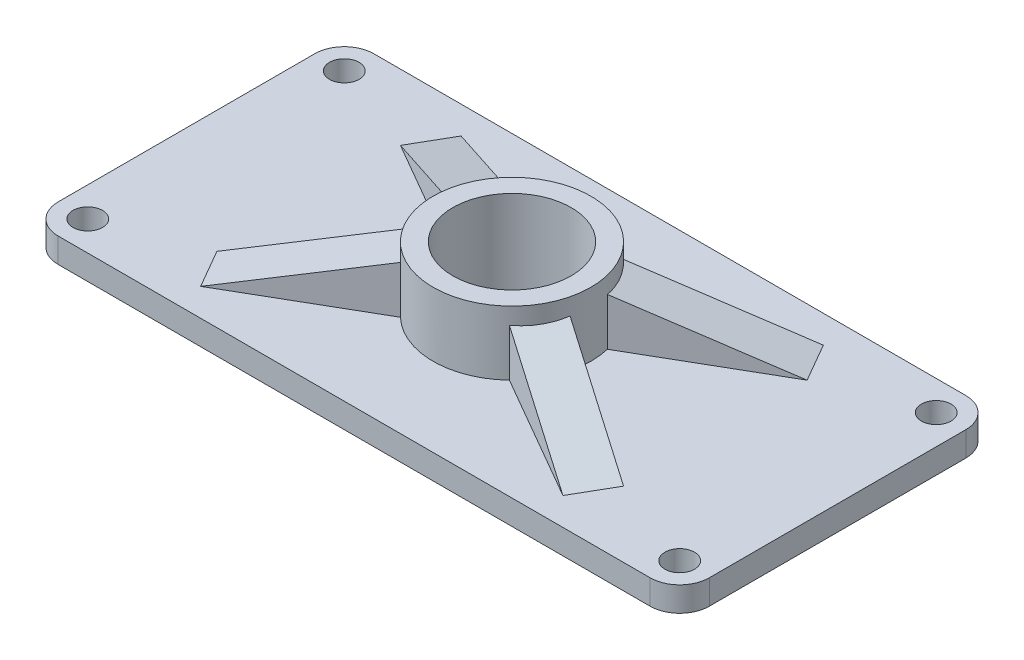
SolidWorks part; units mm, degrees
ref_plane "Front Plane" through (0, 0, 0) normal (0, 0, 1) x (1, 0, 0)
ref_plane "Top Plane" through (0, 0, 0) normal (0, 1, 0) x (1, 0, 0)
ref_plane "Right Plane" through (0, 0, 0) normal (1, 0, 0) x (0, 0, -1)
sketch "Sketch1" plane through (0, 0, 0) normal (0, 1, 0) x (1, 0, 0)
  line L1 (-60, 32) -> (60, 32)
  line L2 (-66, 26) -> (-66, -26)
  line L3 (-60, -32) -> (60, -32)
  line L4 (66, 26) -> (66, -26)
  line L5 (-66, 32) -> (66, -32) construction
  line L6 (-66, -32) -> (66, 32) construction
  arc A0 (60, 32) -> (66, 26) centre (60, 26) cw
  arc A1 (-66, -26) -> (-60, -32) centre (-60, -26) ccw
  arc A2 (-60, 32) -> (-66, 26) centre (-60, 26) ccw
  arc A3 (60, -32) -> (66, -26) centre (60, -26) ccw
  circle A4 centre (-60, 26) radius 3
  circle A5 centre (-60, -26) radius 3
  circle A6 centre (60, 26) radius 3
  circle A7 centre (60, -26) radius 3
  point P0 (0, 0)
  dimension "D3" = 6
  dimension "D4" = 6
  dimension "D5" = 6
  dimension "D6" = 6
  dimension "D7" = 6
  dimension "D1" = 64
  dimension "D2" = 132
extrude "Boss-Extrude1" add sketch "Sketch1" along normal blind 5
sketch "Sketch2" plane through (0, 5, 0) normal (0, 1, 0) x (1, 0, 0)
  circle A0 centre (0, 0) radius 12
  circle A1 centre (0, 0) radius 16
  dimension "D1" = 32
  dimension "D2" = 24
extrude "Cut-Extrude1" cut sketch "Sketch2" against normal blind 5 contours A0
extrude "Boss-Extrude2" add sketch "Sketch2<3>" along normal blind 13
sketch "Sketch2<3>" plane through (0, 5, 0) normal (0, 1, 0) x (1, 0, 0) same geometry as "Sketch2"
sketch "Sketch3" plane through (0, 5, 0) normal (0, 1, 0) x (1, 0, 0)
  line L0 (-75.8789, 0) -> (75.8789, 0) construction
  line L1 (0, -45.5996) -> (0, 45.5996) construction
  line L2 (-79.2846, -45.775) -> (79.2846, 45.775) construction
  line L3 (80.5101, -46.4825) -> (-80.5101, 46.4825) construction
  point P6 (0, 0)
  point P10 (0, 0)
  point P13 (0, 0)
  point P16 (0, 0)
  dimension "D1" = 30
  dimension "D2" = 30
ref_plane "Plane1" through (0, 0, 0) normal (0.5, 0, 0.866) x (0.866, 0, -0.5)
sketch "Sketch4" plane through (0, 0, 0) normal (0.5, 0, 0.866) x (0.866, 0, -0.5)
  line L0 (-45, 5) -> (-14.7048, 14.8435)
  line L1 (-65.7131, 5) -> (65.7131, 5) construction
  line L3 (-14.7048, 14.8435) -> (-14.7048, 5)
  line L4 (-14.7048, 5) -> (-45, 5)
  line L5 (-91.55, 5) -> (91.55, 5) construction
  line L6 (0, 0) -> (0, 36.7155) construction
  line L10 (14.7048, 14.8435) -> (14.7048, 5)
  line L11 (45, 5) -> (14.7048, 14.8435)
  line L12 (14.7048, 5) -> (45, 5)
  point P4 (-14.7048, 14.8435)
  point P5 (12.4471, 15.5719)
  point P16 (-16, 14.4227)
  point P17 (0, 0)
  point P18 (0, 0)
  point P19 (0, 0)
  point P20 (0, 0)
  point P21 (0, 0)
  dimension "D1" = 162
  dimension "D2" = 45
extrude "Boss-Extrude5" add sketch "Sketch4" along normal mid plane 9
mirror "Mirror1" about plane through (0, 0, 0) normal (0, 0, 1) of "Boss-Extrude5"
